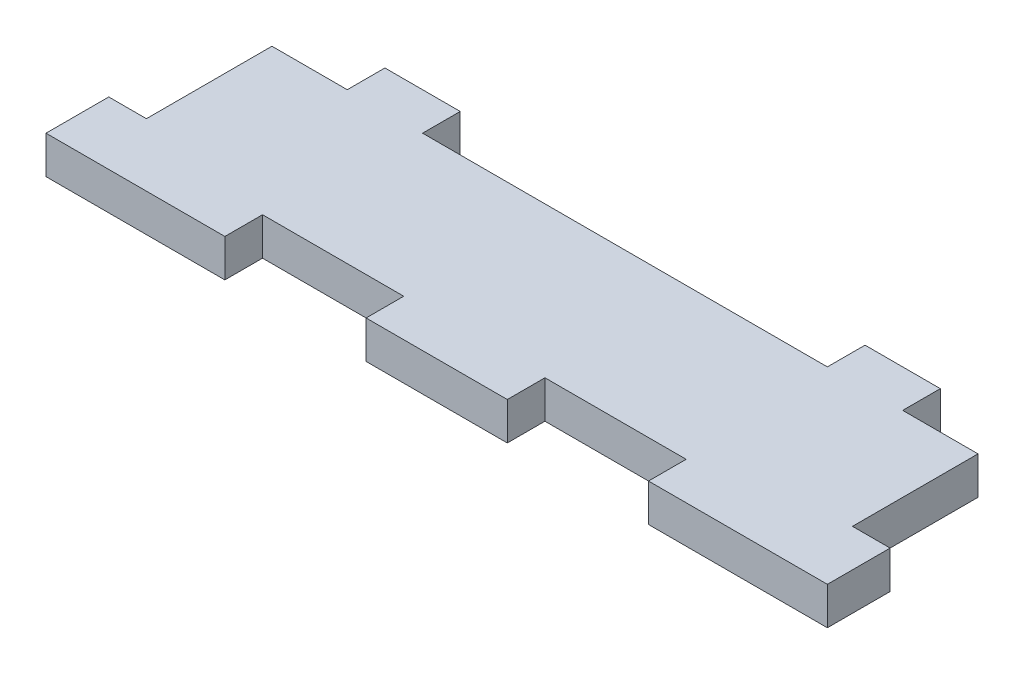
SolidWorks part; units mm, degrees
ref_plane "Front Plane" through (0, 0, 0) normal (0, 0, 1) x (1, 0, 0)
ref_plane "Top Plane" through (0, 0, 0) normal (0, 1, 0) x (1, 0, 0)
ref_plane "Right Plane" through (0, 0, 0) normal (1, 0, 0) x (0, 0, -1)
sketch "Sketch1" plane through (0, 0, 0) normal (0, 1, 0) x (1, 0, 0)
  line L1 (-56.25, -12) -> (56.25, -12)
  line L2 (-56.25, -12) -> (-56.25, 12)
  line L3 (-56.25, 12) -> (56.25, 12)
  line L4 (56.25, -12) -> (56.25, 12)
  line L5 (-56.25, -12) -> (56.25, 12) construction
  line L6 (-56.25, 12) -> (56.25, -12) construction
  point P0 (0, 0)
  dimension "D1" = 112.5
  dimension "D2" = 24
extrude "Boss-Extrude1" add sketch "Sketch1" along normal blind 6
sketch "Sketch2" plane through (0, 0, 12) normal (0, 0, 1) x (1, 0, 0)
  line L0 (-56.25, 6) -> (56.25, 6) construction
  line L1 (-56.25, 0) -> (-33.75, 0)
  line L2 (-56.25, 0) -> (-56.25, 6)
  line L3 (-56.25, 6) -> (-33.75, 6)
  line L4 (-33.75, 0) -> (-33.75, 6)
  line L5 (-56.25, 0) -> (56.25, 0) construction
  line L6 (-33.75, 6) -> (-11.25, 6) construction
  line L7 (-33.75, 6) -> (-33.75, 0) construction
  line L8 (-33.75, 0) -> (-11.25, 0) construction
  line L9 (-11.25, 6) -> (-11.25, 0) construction
  line L11 (-11.25, 0) -> (11.25, 0)
  line L12 (-11.25, 0) -> (-11.25, 6)
  line L13 (-11.25, 6) -> (11.25, 6)
  line L14 (11.25, 0) -> (11.25, 6)
  line L15 (11.25, 6) -> (33.75, 6) construction
  line L16 (11.25, 6) -> (11.25, 0) construction
  line L17 (11.25, 0) -> (33.75, 0) construction
  line L18 (33.75, 6) -> (33.75, 0) construction
  line L19 (33.75, 0) -> (56.25, 0)
  line L20 (33.75, 0) -> (33.75, 6)
  line L21 (33.75, 6) -> (56.25, 6)
  line L22 (56.25, 0) -> (56.25, 6)
extrude "Boss-Extrude2" add sketch "Sketch2" along normal blind 6
sketch "Sketch3" plane through (56.25, 0, 0) normal (1, 0, 0) x (0, 0, -1)
  line L1 (-18, 0) -> (-8, 0)
  line L2 (-18, 0) -> (-18, 6)
  line L3 (-18, 6) -> (-8, 6)
  line L4 (-8, 0) -> (-8, 6)
  line L5 (-18, 6) -> (12, 6) construction
  point P5 (-7.7645, 4.7154)
  point P7 (0, 0)
  dimension "D1" = 10
extrude "Boss-Extrude3" add sketch "Sketch3" along normal blind 6
mirror "Mirror1" about plane through (0, 0, 0) normal (1, 0, 0) of "Boss-Extrude3"
sketch "Sketch4" plane through (0, 0, -12) normal (0, 0, -1) x (-1, 0, 0)
  line L0 (-32.25, 0) -> (32.25, 0)
  line L1 (-56.25, 0) -> (56.25, 0) construction
  line L2 (-56.25, 6) -> (56.25, 6) construction
  line L3 (32.25, 0) -> (44.25, 0)
  line L4 (32.25, 0) -> (32.25, 6)
  line L5 (32.25, 6) -> (44.25, 6)
  line L6 (44.25, 0) -> (44.25, 6)
  line L7 (-32.25, 0) -> (-32.25, 6) construction
  line L8 (-32.25, 0) -> (-44.25, 0)
  line L9 (-32.25, 0) -> (-32.25, 6)
  line L10 (-32.25, 6) -> (-44.25, 6)
  line L11 (-44.25, 0) -> (-44.25, 6)
  line L12 (44.25, 6) -> (44.25, 0) construction
  point P5 (0, 0)
  point P14 (-43.0112, 6)
  point P15 (-32.25, 6)
  point P18 (-43.7593, 6)
  point P19 (-44.0024, 0)
  point P20 (44.25, 0)
  line M9 (-56.25, 0) -> (56.25, 0)
  line M11 (56.25, 6) -> (-56.25, 6)
extrude "Boss-Extrude4" add sketch "Sketch4" along normal blind 6 contours L11 L9 M9 M11 | L6 L4 M9 M11 region at (38.25, 3, -12) region at (-38.25, 3, -12)
